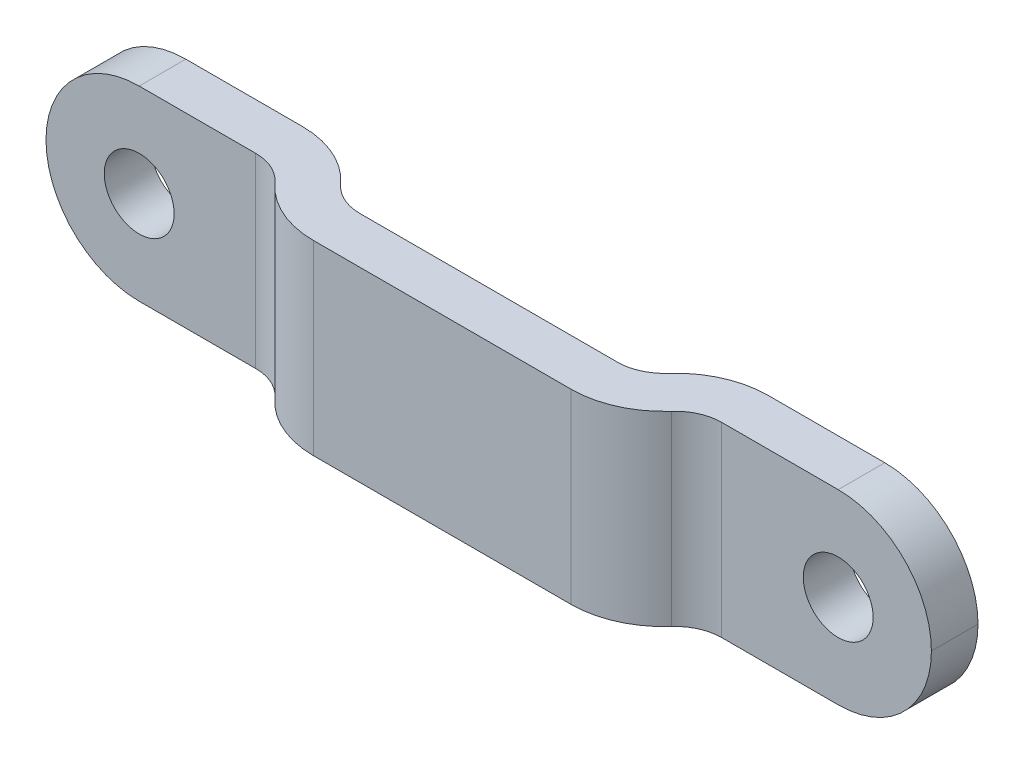
SolidWorks part; units mm, degrees
material "PW20:1:Sc:0:"
ref_plane "front" through (0, 0, 0) normal (0, 0, 1) x (1, 0, 0)
ref_plane "top" through (0, 0, 0) normal (0, 1, 0) x (1, 0, 0)
ref_plane "side" through (0, 0, 0) normal (1, 0, 0) x (0, 0, -1)
other "Configuration Table"
sketch "Sketch1" plane through (0, 0, 0) normal (0, 1, 0) x (1, 0, 0)
  line L0 (-30.1625, 0) -> (-15.875, 0)
  line L1 (-30.1625, 0) -> (-30.1625, -3.175)
  line L2 (-30.1625, -3.175) -> (-15.875, -3.175)
  line L3 (-8.7755, -6.35) -> (8.7755, -6.35)
  line L4 (0, 0) -> (0, 21.9313) construction
  line L5 (-8.7755, -3.175) -> (8.7755, -3.175)
  line L6 (30.1625, -3.175) -> (15.875, -3.175)
  line L7 (30.1625, 0) -> (30.1625, -3.175)
  line L8 (30.1625, 0) -> (15.875, 0)
  line L9 (-50, 0) -> (50, 0) construction
  arc A0 (-15.875, -3.175) -> (-13.5085, -4.2333) centre (-15.875, -6.35) cw
  arc A1 (-13.5085, -4.2333) -> (-8.7755, -6.35) centre (-8.7755, 0) ccw
  arc A2 (-15.875, 0) -> (-11.142, -2.1167) centre (-15.875, -6.35) cw
  arc A3 (-11.142, -2.1167) -> (-8.7755, -3.175) centre (-8.7755, 0) ccw
  arc A4 (11.142, -2.1167) -> (8.7755, -3.175) centre (8.7755, 0) cw
  arc A5 (15.875, 0) -> (11.142, -2.1167) centre (15.875, -6.35) ccw
  arc A6 (13.5085, -4.2333) -> (8.7755, -6.35) centre (8.7755, 0) cw
  arc A7 (15.875, -3.175) -> (13.5085, -4.2333) centre (15.875, -6.35) ccw
  dimension "D5" = 6.35
  dimension "D3" = 6.35
  dimension "D1" = 3.175
  dimension "D2" = 60.325
  dimension "D4" = 31.75
  dimension "D7" = 3.175
extrude "Base-Extrude" add sketch "Sketch1" along normal mid plane 12.7
fillet "Fillet1" radius 6.35 4 edges at (30.1625, 6.35, 1.5875) (30.1625, -6.35, 1.5875) (-30.1625, 6.35, 1.5875) (-30.1625, -6.35, 1.5875)
sketch "Sketch2" plane through (0, 0, 3.175) normal (0, 0, 1) x (1, 0, 0)
  circle A0 centre (23.8125, 0) radius 2.3813
  circle A1 centre (-23.8125, 0) radius 2.3813
  arc A2 (30.1625, 0) -> (23.8125, 6.35) centre (23.8125, 0) ccw construction
  arc A3 (-23.8125, 6.35) -> (-30.1625, 0) centre (-23.8125, 0) ccw construction
  dimension "D1" = 4.7625
extrude "Cut-Extrude1" cut sketch "Sketch2" against normal through all
